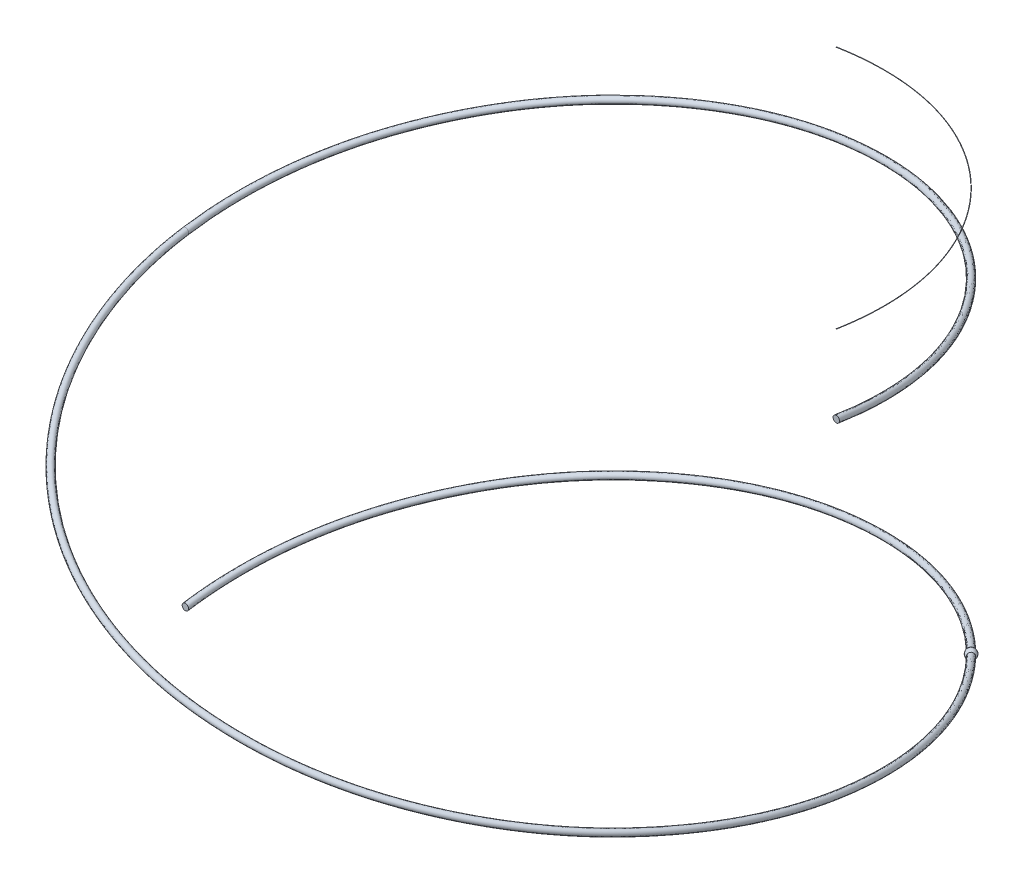
SolidWorks part; units mm, degrees
ref_plane "Front Plane" through (0, 0, 0) normal (0, 0, 1) x (1, 0, 0)
ref_plane "Top Plane" through (0, 0, 0) normal (0, 1, 0) x (1, 0, 0)
ref_plane "Right Plane" through (0, 0, 0) normal (1, 0, 0) x (0, 0, -1)
sketch "Sketch1" plane through (0, 0, 0) normal (0, 1, 0) x (1, 0, 0)
  line L2 (0, 0) -> (-3, 0)
  line L3 (0, 0.0516) -> (0, 3.0516)
  circle A0 centre (0, 0) radius 5 construction
  dimension "D1" = 10
  dimension "D2" = 3
  dimension "D3" = 3
sketch "Sketch3" plane through (0, 0, 0) normal (0, 1, 0) x (1, 0, 0)
  circle A0 centre (0, 0) radius 5 construction
  circle A1 centre (0, 0) radius 5
curve "Helix/Spiral1" pitch 5 height 5 radius 5 left hand yes centre (0, 0, 0) axis (0, 1, 0) start towards (0, 0, 1)
sketch "Sketch4" plane through (0, 0, 0) normal (0, 0, 1) x (1, 0, 0)
  line L0 (-1030.4251, 0) -> (50490.8277, 0) construction
  circle A0 centre (-5, 0) radius 0.05
  dimension "D1" = 5
  dimension "D2" = 0.1
sweep "Sweep1" add profiles "Sketch4" path "Helix/Spiral1"
sketch "Sketch7" plane through (0, 0, 0) normal (0, 0, 1) x (1, 0, 0)
  line L0 (0, -1000) -> (0, 49000)
ref_axis "Axis3" through (0, -1000, 0) along (0, 1, 0)
sketch "Sketch8" plane through (0, 0, 0) normal (0, 1, 0) x (1, 0, 0)
  line L0 (0, 0) -> (35355.3391, 35355.3391) construction
  line L2 (0, 0) -> (-5, 0) construction
  circle A0 centre (0, 0) radius 5 construction
  dimension "D1" = 135
ref_plane "Plane3" through (0, 0, 0) normal (0.7071, 0, 0.7071) x (0.7071, 0, -0.7071)
sketch "Sketch6" plane through (0, 0, 0) normal (0.7071, 0, 0.7071) x (0.7071, 0, -0.7071)
  line L0 (-1000, 0) -> (49000, 0) construction
  line L1 (0, -1000) -> (0, 49000) construction
  line L2 (5, 1.8) -> (5, 1.95)
  line L3 (5, -998.125) -> (5, 49001.875) construction
  line L4 (5, -998.125) -> (5, 49001.875) construction
  arc A0 (5, 1.95) -> (5, 1.8) centre (5, 1.875) ccw
  point P4 (5, 1.875)
  point P6 (5, 1.875)
  point P15 (5, 1.875)
  dimension "D3" = 0.15
  dimension "D1" = 5
  dimension "D2" = 1.875
revolve "Revolve4" add sketch "Sketch6" angle 360 about L3
sketch "Sketch9" plane through (0, 0, 0) normal (0.7071, 0, 0.7071) x (0.7071, 0, -0.7071)
  line L2 (5, 1.875) -> (5, 0) construction
  line L3 (5, 1.8) -> (5, 1.95)
  line L4 (5, 1.8463) -> (5, 1.875)
  line L6 (5, 0) -> (-5, 0) construction
  arc A2 (5, 1.95) -> (5, 1.8) centre (5, 1.875) ccw
  point P9 (5, 1.875)
  dimension "D1" = 0
sketch "Sketch13" plane through (0, 0, 0) normal (0, 0, 1) x (1, 0, 0)
  line L0 (0, 0) -> (0, 6)
  line L1 (0, -1000) -> (0, 49000) construction
  dimension "D1" = 6
sketch "Sketch10" plane through (0, 0, 0) normal (0.7071, 0, 0.7071) x (0.7071, 0, -0.7071)
  line L1 (5, 1.8463) -> (5, 1.875) construction
  line L3 (5, 1.8463) -> (5, 1.875)
  line L4 (0, 0) -> (5, 0) construction
  point P0 (5, 1.875)
sketch "Sketch15" plane through (0, 0, 0) normal (0, 0, -1) x (-1, 0, 0)
  line L0 (-995, 5) -> (49005, 5) construction
  line L1 (5, -995) -> (5, 49005) construction
  point P3 (5, 5)
ref_plane "Plane5" through (0, 5, 0) normal (0, 1, 0) x (1, 0, 0)
sketch "Sketch16" plane through (0, 5, 0) normal (0, 1, 0) x (1, 0, 0)
  circle A0 centre (0, 0) radius 5 construction
  circle A1 centre (0, 0) radius 5
curve "Helix/Spiral2" pitch 5 height 2.5 radius 5 left hand yes centre (0, 5, 0) axis (0, 1, 0) start towards (0, 0, 1)
sketch "Sketch19" plane through (0, 0, 0) normal (0, 1, 0) x (1, 0, 0)
  line L0 (0, 0) -> (-3, 0) construction
  line L1 (-141421.3562, -141421.3562) -> (176776.6953, 176776.6953) construction
  arc A0 (-0.9798, 0.2) -> (0.5514, 0.8342) centre (0, 0) cw
  point P0 (0, 0)
  dimension "D1" = 1
  dimension "D2" = 0.2
  dimension "D3" = 0.2
sketch "Sketch20" plane through (0, 0, 0) normal (0, 1, 0) x (1, 0, 0)
  line L0 (0, -3) -> (0, 0) construction
  line L1 (0, 0) -> (3, 0) construction
  point P0 (0, 0)
  dimension "D1" = 3
  dimension "D2" = 3
sketch "Sketch17" plane through (0, 0, 0) normal (0, 0, -1) x (-1, 0, 0)
  circle A0 centre (5, 5) radius 0.05 construction
  circle A1 centre (5, 5) radius 0.05
sweep "Sweep2" add profiles "Sketch17" path "Helix/Spiral2"
sketch "Sketch22" plane through (0, 0, 0) normal (0, 0, 1) x (1, 0, 0)
  line L0 (0, -1000) -> (0, 49000) construction
  line L1 (200995, 5) -> (-249005, 5) construction
  line L2 (5, 7.7) -> (5, 9.7)
  point P0 (5, 7.5)
  dimension "D1" = 5
  dimension "D2" = 2.5
  dimension "D3" = 0.2
  dimension "D4" = 2
sketch "Sketch23" plane through (0, 0, 0) normal (0, 0, 1) x (1, 0, 0)
  line L0 (5, 7.7) -> (5, 9.7) construction
  point P0 (5, 8.7)
ref_plane "Plane7" through (0, 8.7, 0) normal (0, 1, 0) x (1, 0, 0)
sketch "Sketch24" [suppressed] plane through (0, 8.7, 0) normal (0, 1, 0) x (1, 0, 0)
  arc A0 (5, 0) -> (2.3641, 4.4058) centre (0, 0) ccw
sketch "Sketch28" plane through (0, 8.7, 0) normal (0, 1, 0) x (1, 0, 0)
  circle A0 centre (0, 0) radius 5
curve "Helix/Spiral4" pitch 5 height 1.25 radius 5 left hand yes centre (0, 8.7, 0) axis (0, -1, 0) start towards (1, 0, 0)
sketch "Sketch29" plane through (0, 0, 0) normal (0, 0, 1) x (1, 0, 0)
  circle A0 centre (5, 8.7) radius 0.0025
  dimension "D1" = 0.005
sweep "Sweep3" add profiles "Sketch29" path "Helix/Spiral4"
sketch "Sketch30" plane through (0, 0, 0) normal (0, 1, 0) x (1, 0, 0)
  line L0 (-5.3, 0) -> (-7.3, 0)
  line L1 (200995, 0) -> (-249005, 0) construction
  line L2 (3.7477, 3.7477) -> (5.1619, 5.1619)
  line L3 (-141421.3562, -141421.3562) -> (176776.6953, 176776.6953) construction
  arc A0 (-6.3, 0) -> (4.4548, 4.4548) centre (0, 0) cw construction
  dimension "D1" = 2
  dimension "D2" = 5.3
  dimension "D3" = 2
  dimension "D4" = 5.3
sketch "Sketch21" plane through (0, 0, 0) normal (0, 0, 1) x (1, 0, 0)
  line L0 (5, 7.5) -> (5, 9.5)
  point P0 (5, 7.5)
  point P3 (5, 8.5)
  dimension "D1" = 2
  dimension "D2" = 1
ref_plane "Plane6" through (0, 8.5, 0) normal (0, 1, 0) x (1, 0, 0)
sketch "Sketch12" plane through (0, 0, 0) normal (0, 0, 1) x (1, 0, 0)
  line L1 (0, 0) -> (-5, 0)
